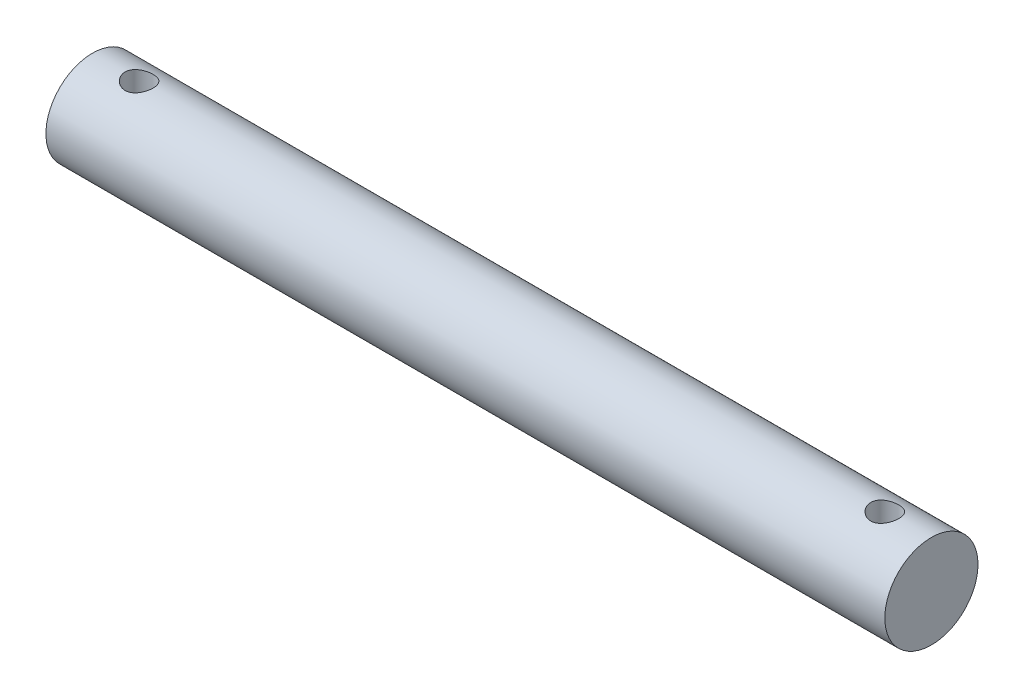
SolidWorks part; units mm, degrees
material "Plywood"
ref_plane "Front Plane" through (0, 0, 0) normal (0, 0, 1) x (1, 0, 0)
ref_plane "Top Plane" through (0, 0, 0) normal (0, 1, 0) x (1, 0, 0)
ref_plane "Right Plane" through (0, 0, 0) normal (1, 0, 0) x (0, 0, -1)
sketch "Sketch1" plane through (0, 0, 0) normal (1, 0, 0) x (0, 0, -1)
  circle A0 centre (0, 0) radius 5
  dimension "D1" = 10
extrude "Boss-Extrude1" add sketch "Sketch1" along normal mid plane 90
sketch "Sketch4" plane through (0, 0, 0) normal (0, 1, 0) x (1, 0, 0)
  line L0 (-45, 5) -> (-45, -5) construction
  circle A0 centre (-40, 0) radius 1.5
  dimension "D1" = 3
  dimension "D2" = 5
extrude "Cut-Extrude1" cut sketch "Sketch4" against normal through all both and the other way through all
ref_axis "Axis1" through (-40, -5, 0) along (0, 1, 0)
ref_plane "Plane1" through (-37, 0, 0) normal (-1, 0, 0) x (0, 0, 1)
mirror "Mirror1" about plane through (0, 0, 0) normal (1, 0, 0) of "Cut-Extrude1"
